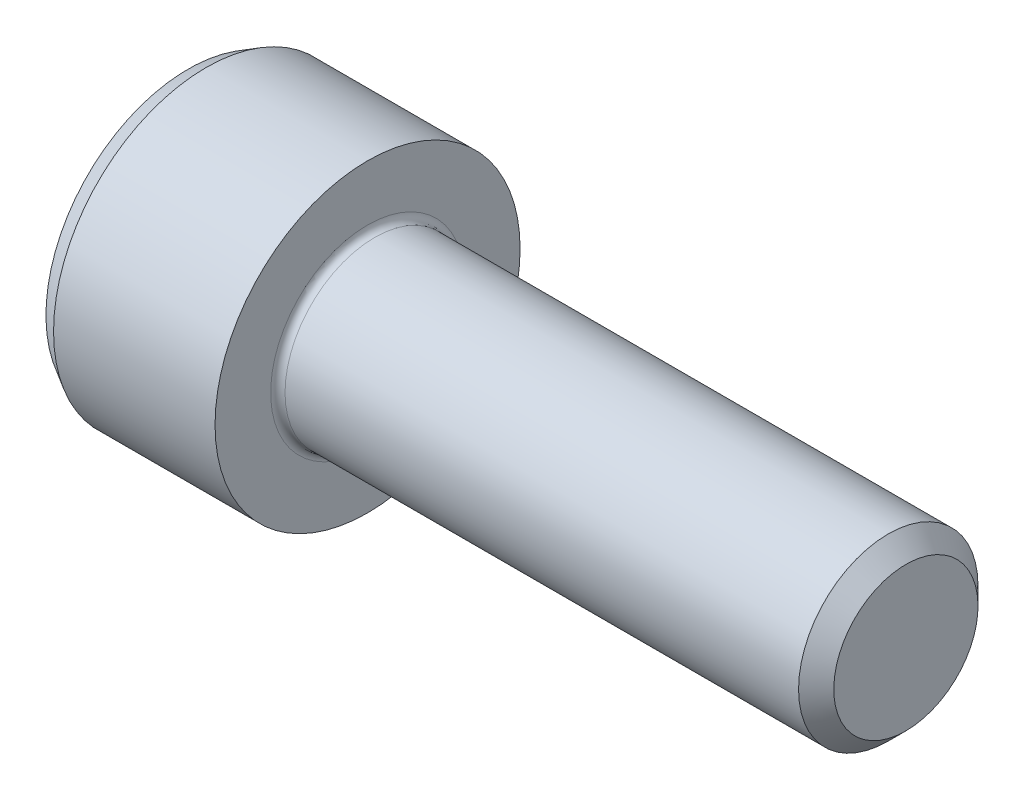
SolidWorks part; units mm, degrees
material "A6061"
ref_plane "前视基准面" through (0, 0, 0) normal (0, 0, 1) x (1, 0, 0)
ref_plane "上视基准面" through (0, 0, 0) normal (0, 1, 0) x (1, 0, 0)
ref_plane "右视基准面" through (0, 0, 0) normal (1, 0, 0) x (0, 0, -1)
ref_plane "基准面1" through (0, 0, 0) normal (0, 0, 1) x (1, 0, 0)
sketch "草图1" plane through (0, 0, 0) normal (0, 0, 1) x (1, 0, 0)
  line L0 (-5, 0) -> (-5, 3.9613)
  line L1 (-5, 3.9613) -> (-4.5, 4.25)
  line L2 (-4.5, 4.25) -> (0, 4.25)
  line L3 (0, 4.25) -> (0, 2.7)
  line L4 (0.2, 2.5) -> (14.5095, 2.5)
  line L5 (14.5095, 2.5) -> (15, 2.0095)
  line L6 (15, 2.0095) -> (15, 0)
  line L7 (15, 0) -> (-5, 0)
  line L8 (15, 0) -> (-5, 0) construction
  arc A0 (0, 2.7) -> (0.2, 2.5) centre (0.2, 2.7) ccw
revolve "旋转1" add sketch "草图1" angle 360 about L8 reverse direction yes
cosmetic thread "装饰螺纹线1" parameters "D1"=14.8, "D2"=4.019
sketch "草图2" plane through (0, 0, 0) normal (0, 0, 1) x (1, 0, 0)
  line L0 (-5, 0) -> (-5, 2)
  line L1 (-5, 2) -> (-2.5, 2)
  line L2 (-2.5, 2) -> (-1.3453, 0)
  line L3 (-1.3453, 0) -> (-5, 0)
  line L4 (-1.3453, 0) -> (-5, 0) construction
revolve "切除-旋转1" cut sketch "草图2" angle 360 about L4 reverse direction yes
ref_plane "基准面2" through (-5, 0, 0) normal (1, 0, 0) x (0, 0, -1)
sketch "草图3" plane through (-5, 0, 0) normal (1, 0, 0) x (0, 0, -1)
  line L0 (-2, -1.1547) -> (0, -2.3094)
  line L1 (0, -2.3094) -> (2, -1.1547)
  line L2 (2, -1.1547) -> (2, 1.1547)
  line L3 (2, 1.1547) -> (0, 2.3094)
  line L4 (0, 2.3094) -> (-2, 1.1547)
  line L5 (-2, 1.1547) -> (-2, -1.1547)
extrude "切除-拉伸1" cut sketch "草图3" along normal blind 2.5
ref_plane "基准面3" through (15, 0, 0) normal (1, 0, 0) x (0, 0, -1)
ref_plane "bolt XY" through (0, 0, 0) normal (1, 0, 0) x (0, 0, -1)
ref_plane "bolt XZ" through (0, 0, 0) normal (0, -1, 0) x (-1, 0, 0)
ref_plane "bolt YZ" through (0, 0, 0) normal (0, 0, -1) x (-1, 0, 0)
ref_axis "bolt X" through (0, 0, 80.9) along (0, 0, -1)
ref_axis "bolt Y" through (0, -50, 0) along (0, 1, 0)
ref_axis "bolt Z" through (80.9, 0, 0) along (-1, 0, 0)
sketch3d "bolt"
  point P0 (0, 0, 0)
ref_plane "nut XY" through (15, 0, 0) normal (1, 0, 0) x (0, 0, -1)
ref_plane "nut XZ" through (0, 0, 0) normal (0, -1, 0) x (-1, 0, 0)
ref_plane "nut YZ" through (0, 0, 0) normal (0, 0, -1) x (-1, 0, 0)
ref_axis "nut X" through (15, 0, 80.9) along (0, 0, -1)
ref_axis "nut Y" through (15, -50, 0) along (0, 1, 0)
ref_axis "nut Z" through (80.9, 0, 0) along (-1, 0, 0)
sketch3d "nut"
  point P0 (15, 0, 0)
